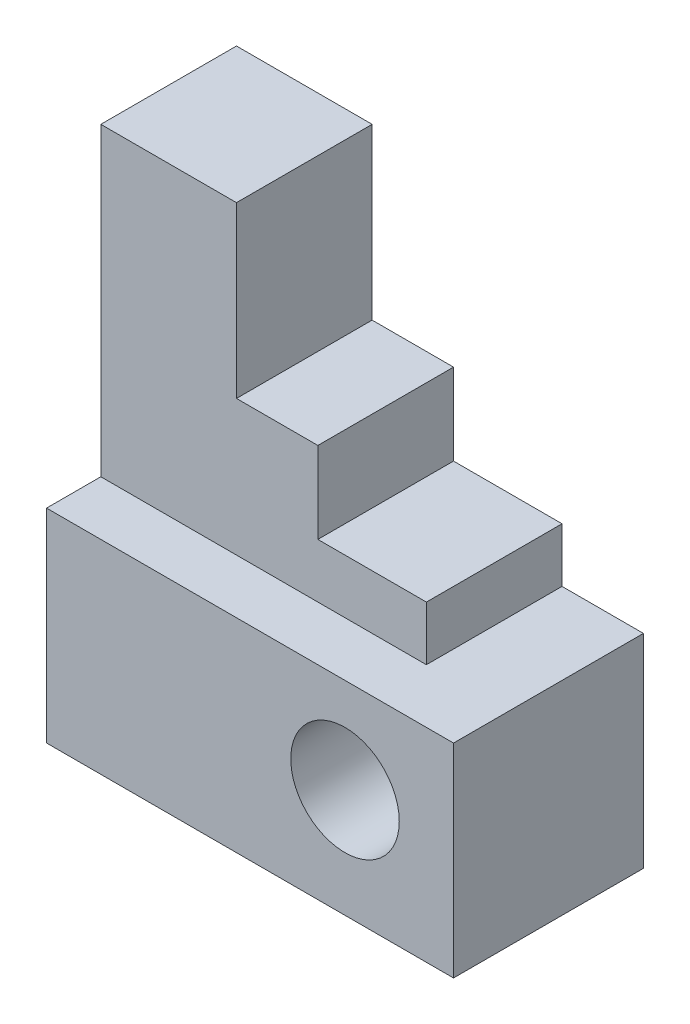
SolidWorks part; units mm, degrees
material "Aluminum Bronze"
ref_plane "Front Plane" through (0, 0, 0) normal (0, 0, 1) x (1, 0, 0)
ref_plane "Top Plane" through (0, 0, 0) normal (0, 1, 0) x (1, 0, 0)
ref_plane "Right Plane" through (0, 0, 0) normal (1, 0, 0) x (0, 0, -1)
sketch "Sketch1" plane through (0, 0, 0) normal (0, 0, 1) x (1, 0, 0)
  line L1 (0, 0) -> (60, 0)
  line L2 (0, 0) -> (0, 30)
  line L3 (0, 30) -> (60, 30)
  line L4 (60, 0) -> (60, 30)
  circle A0 centre (44, 16) radius 8
  dimension "D3" = 16
  dimension "D1" = 60
  dimension "D2" = 30
  dimension "D4" = 16
  dimension "D5" = 16
extrude "Boss-Extrude1" add sketch "Sketch1" along normal blind 28
sketch "Sketch2" plane through (0, 0, 0) normal (0, 0, 1) x (1, 0, 0)
  line L0 (0, 30) -> (0, 75)
  line L1 (0, 75) -> (20, 75)
  line L2 (20, 75) -> (20, 50)
  line L3 (20, 50) -> (32, 50)
  line L4 (32, 50) -> (32, 38)
  line L5 (32, 38) -> (48, 38)
  line L6 (48, 38) -> (48, 30)
  line L7 (60, 30) -> (0, 30) construction
  line L8 (48, 30) -> (0, 30)
  line L9 (0, 0) -> (60, 0) construction
  line L10 (60, 0) -> (60, 30) construction
  dimension "D1" = 75
  dimension "D2" = 12
  dimension "D3" = 12
  dimension "D4" = 12
  dimension "D5" = 20
  dimension "D6" = 20
extrude "Boss-Extrude2" add sketch "Sketch2" along normal blind 20
